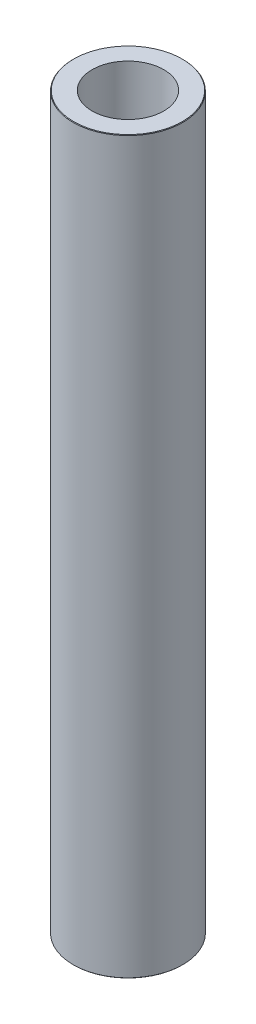
SolidWorks part; units mm, degrees
ref_plane "Front Plane" through (0, 0, 0) normal (0, 0, 1) x (1, 0, 0)
ref_plane "Top Plane" through (0, 0, 0) normal (0, 1, 0) x (1, 0, 0)
ref_plane "Right Plane" through (0, 0, 0) normal (1, 0, 0) x (0, 0, -1)
sketch "Sketch1" plane through (0, 0, 0) normal (0, 1, 0) x (1, 0, 0)
  circle A0 centre (0, 0) radius 45
  dimension "SHAFT_OD" = 90
extrude "Boss-Extrude1" add sketch "Sketch1" along normal blind 600
sketch "Sketch2" plane through (0, 0, 0) normal (0, 1, 0) x (1, 0, 0)
  circle A0 centre (0, 0) radius 29.448
  dimension "BORE_D" = 58.8959
extrude "Cut-Extrude1" cut sketch "Sketch2" along normal through all
chamfer "Chamfer1" distance 0.4234 angle 45 2 edges at (0, 600, 45) (0, 0, 45)
